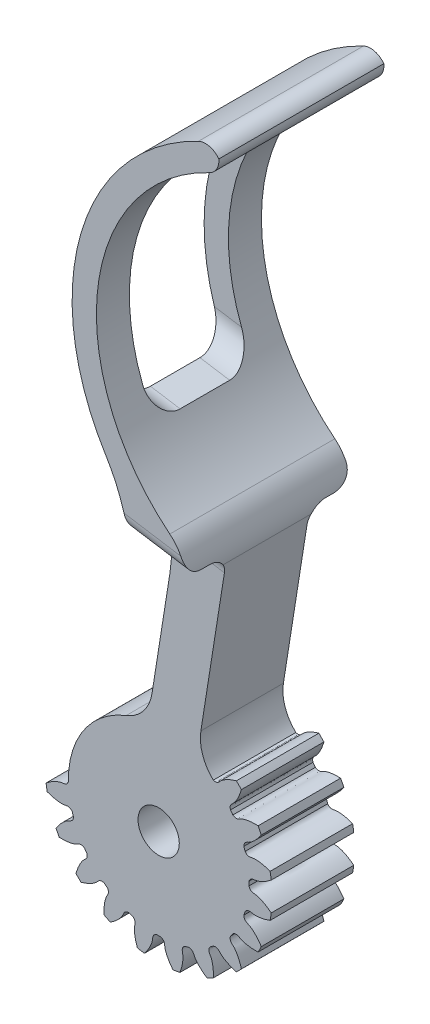
SolidWorks part; units mm, degrees
material "聚脂树脂"
ref_plane "前视基准面" through (0, 0, 0) normal (0, 0, 1) x (1, 0, 0)
ref_plane "上视基准面" through (0, 0, 0) normal (0, 1, 0) x (1, 0, 0)
ref_plane "右视基准面" through (0, 0, 0) normal (1, 0, 0) x (0, 0, -1)
other "Configuration Table"
sketch "草图1" plane through (0, 0, 0) normal (0, 0, 1) x (1, 0, 0)
  circle A0 centre (0, 0) radius 13.75
extrude "凸台-拉伸1" add sketch "草图1" along normal blind 10
ref_axis "基准轴1" through (0, 0, -1.5) along (0, 0, 1)
sketch "草图2" plane through (0, 0, 0) normal (0, 0, 1) x (1, 0, 0)
  line L0 (0, 0) -> (0, 13.75) construction
  circle A0 centre (0, 0) radius 13.75 construction
  arc A1 (0.2416, 10.9348) -> (-0.2416, 10.9348) centre (0, 0) ccw
  arc A2 (3.9764, 15.6228) -> (-3.9764, 15.6228) centre (0, 0) ccw
  spline S0 degree 3 poles (0.2416, 10.9348) (0.764, 11.1168) (0.6964, 11.4839) (0.7661, 11.8375) (0.7736, 11.8719) (0.7829, 11.9108) (0.7941, 11.954) (0.8075, 12.0015) (0.8231, 12.0532) (0.8413, 12.1091) (0.8621, 12.169) (0.8857, 12.2329) (0.9123, 12.3007) (0.9421, 12.3723) (0.9752, 12.4476) (1.0117, 12.5264) (1.0519, 12.6088) (1.0959, 12.6945) (1.1438, 12.7834) (1.1957, 12.8755) (1.2519, 12.9705) (1.3125, 13.0684) (1.3775, 13.1691) (1.4472, 13.2723) (1.5216, 13.3779) (1.601, 13.4858) (1.6853, 13.5958) (1.7747, 13.7078) (1.8694, 13.8216) (1.9693, 13.937) (2.0748, 14.0539) (2.1857, 14.1721) (2.3023, 14.2914) (2.4246, 14.4116) (2.5527, 14.5326) (2.6866, 14.6542) (2.8265, 14.7761) (2.9725, 14.8983) (3.1245, 15.0204) (3.2826, 15.1424) (3.4469, 15.2639) (3.6768, 15.427) (3.8549, 15.5454) (3.9764, 15.6228) knots 0 0 0 0 0.165916 0.170906 0.176664 0.183189 0.190482 0.198542 0.207371 0.216967 0.22733 0.238462 0.250361 0.263027 0.276462 0.290664 0.305634 0.321371 0.337876 0.355149 0.37319 0.391998 0.411574 0.431917 0.453028 0.474907 0.497554 0.520968 0.54515 0.570099 0.595817 0.622302 0.649554 0.677575 0.706363 0.735918 0.766242 0.797333 0.829191 0.861818 0.895212 0.929373 1 1 1 1
  spline S1 degree 3 poles (-0.2416, 10.9348) (-0.764, 11.1168) (-0.6964, 11.4839) (-0.7661, 11.8375) (-0.7736, 11.8719) (-0.7829, 11.9108) (-0.7941, 11.954) (-0.8075, 12.0015) (-0.8231, 12.0532) (-0.8413, 12.1091) (-0.8621, 12.169) (-0.8857, 12.2329) (-0.9123, 12.3007) (-0.9421, 12.3723) (-0.9752, 12.4476) (-1.0117, 12.5264) (-1.0519, 12.6088) (-1.0959, 12.6945) (-1.1438, 12.7834) (-1.1957, 12.8755) (-1.2519, 12.9705) (-1.3125, 13.0684) (-1.3775, 13.1691) (-1.4472, 13.2723) (-1.5216, 13.3779) (-1.601, 13.4858) (-1.6853, 13.5958) (-1.7747, 13.7078) (-1.8694, 13.8216) (-1.9693, 13.937) (-2.0748, 14.0539) (-2.1857, 14.1721) (-2.3023, 14.2914) (-2.4246, 14.4116) (-2.5527, 14.5326) (-2.6866, 14.6542) (-2.8265, 14.7761) (-2.9725, 14.8983) (-3.1245, 15.0204) (-3.2826, 15.1424) (-3.4469, 15.2639) (-3.6768, 15.427) (-3.8549, 15.5454) (-3.9764, 15.6228) knots 0 0 0 0 0.165916 0.170906 0.176664 0.183189 0.190482 0.198542 0.207371 0.216967 0.22733 0.238462 0.250361 0.263027 0.276462 0.290664 0.305634 0.321371 0.337876 0.355149 0.37319 0.391998 0.411574 0.431917 0.453028 0.474907 0.497554 0.520968 0.54515 0.570099 0.595817 0.622302 0.649554 0.677575 0.706363 0.735918 0.766242 0.797333 0.829191 0.861818 0.895212 0.929373 1 1 1 1
extrude "切除-拉伸1" cut sketch "草图2" along normal through all
pattern_circular "阵列(圆周)1" count 20 every 18 about axis through (0, 0, -1.5) along (0, 0, 1) of "切除-拉伸1"
sketch "草图3" plane through (0, 0, 0) normal (0, 0, 1) x (1, 0, 0)
  circle A0 centre (0, 0) radius 12.5 construction
  dimension "Dn" = 25
sketch "草图6" plane through (0, 0, 0) normal (0, 0, -1) x (-1, 0, 0)
  line L0 (0, 0) -> (-10.311, 65.1009) construction
  line L1 (0, 0) -> (38.9643, 6.1713) construction
  line L2 (0, 0) -> (-30.4582, -4.8241) construction
  line L3 (-12.3461, -1.9554) -> (-21.1812, 53.827) construction
  line L4 (2.9631, 0.4693) -> (-2.6968, 36.2041)
  line L5 (-2.9631, -0.4693) -> (-8.6229, 35.2655)
  line L6 (-8.6229, 35.2655) -> (-14.6447, 73.2858)
  line L7 (-14.6447, 73.2858) -> (-21.4537, 55.5478) construction
  line L8 (-14.6447, 73.2858) -> (-7.9754, 90.6601) construction
  line L9 (-14.6447, 73.2858) -> (-11.7977, 80.7025)
  line L10 (-2.9631, -0.4693) -> (2.9631, 0.4693)
  circle A0 centre (0, 0) radius 12.5 construction
  circle A1 centre (-21.4537, 55.5478) radius 24 construction
  circle A2 centre (-21.4537, 55.5478) radius 26.9444 construction
  arc A3 (-11.7977, 80.7025) -> (-2.6968, 36.2041) centre (-21.4537, 55.5478) cw
  arc A4 (-12.8529, 77.9537) -> (-8.6229, 35.2655) centre (-21.4537, 55.5478) cw
  dimension "D1" = 25
  dimension "D4" = 48
  dimension "D5" = 30
  dimension "D2" = 6
  dimension "D3" = 58.22
extrude "凸台-拉伸2" add sketch "草图6" against normal blind 15 and the other way blind 5 contours A3 L9 L6 L5 L10 L4 | L5 | L4 region at (0.1302, 0.8219, 0)
sketch "草图7" plane through (-2.9631, 0.4693, 0) normal (0.9877, -0.1564, 0) x (0, 0, -1)
  line L0 (0, 0) -> (0, 34)
  line L1 (0, 34) -> (5, 34)
  line L3 (5, 34) -> (5, 0)
  line L4 (5, 0) -> (0, 0) construction
  line L5 (5, 0) -> (5, 36.1803) construction
  line L6 (5, 0) -> (0, 0)
  line L7 (-5, 4.6588) -> (-5, 27.3083) construction
  line L8 (-10, 4.6588) -> (0, 4.6588) construction
  line L9 (-15, 34) -> (-15, 0)
  line L10 (-10, 34) -> (-15, 34)
  line L11 (-10, 0) -> (-10, 34)
  line L12 (-15, 0) -> (-10, 0)
  dimension "D1" = 34
extrude "切除-拉伸3" cut sketch "草图7" against normal blind 32 and the other way blind 10
ref_plane "基准面1" through (12.5, 0, 0) normal (1, 0, 0) x (0, 0, -1)
ref_axis "基准轴2" through (0, 0, -6) along (0, 0, 1)
ref_plane "基准面2" through (0, 0, 0) normal (-0.9877, 0.1564, 0) x (0, 0, 1)
ref_plane "基准面3" through (12.3461, -1.9554, 0) normal (-0.9877, 0.1564, 0) x (0, 0, 1)
fillet "圆角2" radius 2 4 edges at (5.3188, 33.5814, 10) (5.3188, 33.5814, 15) (5.3188, 33.5814, 0) (5.3188, 33.5814, -5)
sketch "草图16" plane through (0, 0, 10) normal (0, 0, 1) x (1, 0, 0)
  circle A0 centre (0, 0) radius 2.5
  dimension "D1" = 5
extrude "切除-拉伸5" cut sketch "草图16" against normal blind 16.5
sketch "草图19" plane through (0, 0, 0) normal (0, 0, -1) x (-1, 0, 0)
  circle A0 centre (0, 0) radius 8
  dimension "D1" = 16
extrude "切除-拉伸7" cut sketch "草图19" against normal blind 3.4
sketch "草图20" plane through (0, 0, 0) normal (0, 0, -1) x (-1, 0, 0)
  line L0 (0, 0) -> (3.6089, 10.325)
  line L1 (3.6089, 10.325) -> (7.1451, 20.4421)
  line L2 (0, 0) -> (10.9348, -0.2416)
  line L3 (10.9348, -0.2416) -> (20.7519, -0.2416)
  circle A0 centre (0, 0) radius 17.5
  circle A1 centre (0, 0) radius 10.9375
  arc A2 (-8.7044, 6.6228) -> (-8.9885, 6.2318) centre (0, 0) ccw construction
  dimension "D1" = 35
extrude "切除-拉伸8" cut sketch "草图20" against normal blind 10 contours A1 L3 A0 L1 region at (-11.1082, 7.7459, 0)
fillet "圆角3" radius 20 1 edges at (2.6968, 36.2041, 5)
fillet "圆角4" radius 5 1 edges at (8.6229, 35.2655, 5)
fillet "圆角5" radius 2 2 edges at (12.8529, 77.9537, 5) (11.7977, 80.7025, 5)
sketch "草图22" plane through (12.3461, -1.9554, 0) normal (-0.9877, 0.1564, 0) x (0, 0, 1)
  line L0 (5, -1.9493) -> (5, 109.7629) construction
  line L1 (10, -1.9493) -> (0, -1.9493) construction
  line L2 (-5, 80.3992) -> (-5, 40.5896) construction
  line L5 (-1, 43.22) -> (11, 43.22)
  line L6 (-1, 43.22) -> (-1, 73.22)
  line L7 (-1, 73.22) -> (11, 73.22)
  line L8 (11, 43.22) -> (11, 73.22)
  line L9 (-1, 43.22) -> (11, 73.22) construction
  line L10 (-1, 73.22) -> (11, 43.22) construction
  point P4 (5, 58.22)
  dimension "D1" = 58.22
  dimension "D2" = 4
  dimension "D3" = 30
extrude "切除-拉伸9" cut sketch "草图22" along normal blind 45
fillet "圆角6" radius 3 4 edges at (-1.1987, 43.9486, 11) (-1.1987, 43.9486, -1) (3.4943, 73.5792, -1) (3.4943, 73.5792, 11)
sketch "草图23" plane through (0, 0, 10) normal (0, 0, 1) x (1, 0, 0)
  line L0 (-1.0432, 12.5907) -> (-1.3177, 10.8578)
  line L1 (1.3394, 27.6338) -> (-1.0432, 12.5907) construction
  line L2 (4.8829, 11.6521) -> (4.6084, 9.9192)
  line L3 (7.969, 31.1367) -> (4.8829, 11.6521) construction
  circle A0 centre (0, 0) radius 10.9375
  arc A1 (-1.7221, 13.6417) -> (-2.5777, 13.5062) centre (0, 0) ccw construction
  arc A2 (-1.7221, 13.6417) -> (-2.5777, 13.5062) centre (0, 0) ccw
  arc A3 (6.6252, 12.0486) -> (5.8534, 12.4419) centre (0, 0) ccw construction
  arc A4 (6.6252, 12.0486) -> (5.8534, 12.4419) centre (0, 0) ccw
  spline S0 degree 3 poles (996.9002, 66.1041) (-88.8946, -5.2942) (-13.4757, 28.9809) (-1.5748, 13.4516) (-1.4488, 13.2768) (-1.314, 13.073) (-1.1971, 12.8801) (-1.1119, 12.7258) (4.1756, 2.4179) (-28.4054, -26.7623) (-988.0977, -147.6932) knots -9.021594 -9.021594 -9.021594 -9.021594 0.502446 0.525093 0.568083 0.608002 0.644851 0.678629 0.694366 6.323146 6.323146 6.323146 6.323146 only from (-1.7221, 13.6417) to (-1.0432, 12.5907) construction
  spline S1 degree 3 poles (-1001.8702, -39.9652) (14.2454, 6.0691) (-2.4742, 7.7001) (-2.931, 11.5081) (-2.9354, 11.558) (-2.9398, 11.6323) (-2.9424, 11.7223) (-2.941, 11.8445) (-2.9339, 11.9853) (-2.9194, 12.1444) (-2.8961, 12.3215) (-2.8626, 12.516) (-2.8175, 12.7274) (-2.7593, 12.9551) (-2.6999, 13.1539) (-2.6447, 13.3205) (3.8605, 31.7266) (86.1798, 22.4348) (-968.5361, -245.1905) knots -1.696649 -1.696649 -1.696649 -1.696649 0.165916 0.170906 0.183189 0.190482 0.207371 0.22733 0.250361 0.276462 0.305634 0.337876 0.37319 0.411574 0.453028 0.474907 0.497554 10.021595 10.021595 10.021595 10.021595 only from (-3.1492, 10.4743) to (-2.5777, 13.5062) construction
  spline S2 degree 3 poles (-1.7221, 13.6417) (-1.653, 13.5549) (-1.5348, 13.399) (-1.3791, 13.1737) (-1.2534, 12.9751) (-1.1451, 12.788) (-1.078, 12.6606) (-1.046, 12.5962) (-1.0432, 12.5907) knots 0.492568 0.492568 0.492568 0.492568 0.546972 0.588426 0.62681 0.662124 0.694366 0.697389 0.697389 0.697389 0.697389
  spline S3 degree 3 poles (-3.1492, 10.4743) (-2.7087, 10.8088) (-2.8864, 11.137) (-2.931, 11.5081) (-2.9354, 11.558) (-2.9398, 11.6323) (-2.9424, 11.7223) (-2.941, 11.8445) (-2.9339, 11.9853) (-2.9194, 12.1444) (-2.8961, 12.3215) (-2.8626, 12.516) (-2.8175, 12.7274) (-2.7593, 12.9551) (-2.6866, 13.1982) (-2.6232, 13.3832) (-2.5848, 13.4873) (-2.5777, 13.5062) knots 0 0 0 0 0.165916 0.170906 0.183189 0.190482 0.207371 0.22733 0.250361 0.276462 0.305634 0.337876 0.37319 0.411574 0.453028 0.497554 0.507432 0.507432 0.507432 0.507432
  spline S4 degree 3 poles (845.3644, -532.484) (-75.0291, 47.9678) (6.1325, 31.3668) (6.6326, 11.8082) (6.6318, 11.5928) (6.6211, 11.3487) (6.6022, 11.1239) (6.5767, 10.9187) (6.5461, 10.7332) (6.5119, 10.5675) (6.4757, 10.4216) (6.4439, 10.3125) (6.4137, 10.2194) (6.3905, 10.1545) (6.3633, 10.0853) (6.3437, 10.0391) (4.7326, 6.5586) (-11.6727, 10.1742) (940.4849, -347.6039) knots -9.021595 -9.021595 -9.021595 -9.021595 0.502446 0.525093 0.568083 0.608002 0.644851 0.678629 0.709336 0.736973 0.761538 0.783033 0.792629 0.809518 0.816811 0.829094 0.834084 2.696649 2.696649 2.696649 2.696649 only from (6.6252, 12.0486) to (6.2318, 8.9885) construction
  spline S5 degree 3 poles (894.1115, -445.8104) (18.7454, -34.2306) (-3.2241, 3.5899) (4.99, 11.7594) (5.1187, 11.8798) (5.2895, 12.0271) (5.4807, 12.1793) (5.6544, 12.3066) (21.7717, 23.3982) (82.9075, -32.5048) (-927.6753, 370.9255) knots -5.323178 -5.323178 -5.323178 -5.323178 0.305634 0.321371 0.355149 0.391998 0.431917 0.474907 0.497554 10.021576 10.021576 10.021576 10.021576 only from (4.8829, 11.6521) to (5.8534, 12.4419) construction
  spline S6 degree 3 poles (6.6252, 12.0486) (6.6301, 11.9377) (6.6341, 11.7422) (6.6276, 11.4683) (6.6126, 11.2338) (6.5902, 11.0188) (6.5619, 10.8235) (6.5293, 10.6479) (6.4939, 10.4921) (6.4623, 10.3749) (6.4317, 10.2737) (6.4078, 10.2024) (6.3839, 10.1378) (6.3633, 10.0853) (6.3437, 10.0391) (6.1867, 9.7) (5.9162, 9.4428) (6.2318, 8.9885) knots 0.492568 0.492568 0.492568 0.492568 0.546972 0.588426 0.62681 0.662124 0.694366 0.723538 0.749639 0.77267 0.783033 0.801458 0.809518 0.816811 0.829094 0.834084 1 1 1 1
  spline S7 degree 3 poles (4.8829, 11.6521) (4.9332, 11.7035) (5.0362, 11.8042) (5.2016, 11.9528) (5.3825, 12.1027) (5.5842, 12.2567) (5.7442, 12.3691) (5.8366, 12.4308) (5.8534, 12.4419) knots 0.302611 0.302611 0.302611 0.302611 0.337876 0.37319 0.411574 0.453028 0.497554 0.507432 0.507432 0.507432 0.507432
extrude "切除-拉伸10" cut sketch "草图23" against normal blind 10 contours S3 A0 L0 S2 A2 | S7 L2 A0 S6 A4 region at (-2.0521, 12.0792, 10) region at (5.6844, 10.8538, 10)
fillet "圆角7" radius 5 2 edges at (4.6084, 9.9192, 5) (-1.3177, 10.8578, 5)
